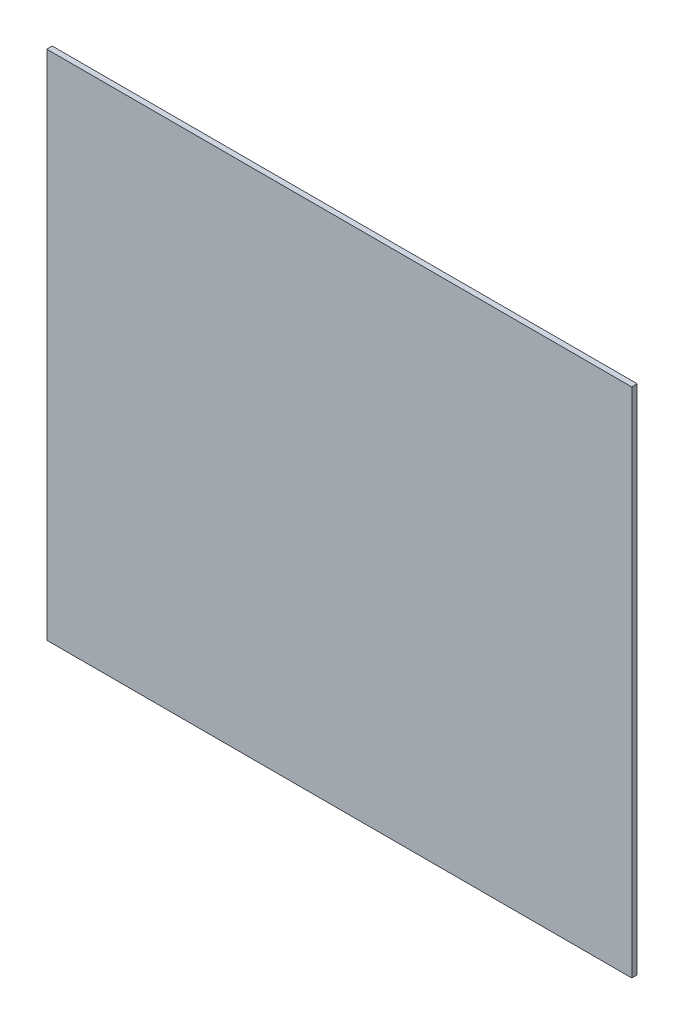
SolidWorks part; units mm, degrees
ref_plane "Front Plane" through (0, 0, 0) normal (0, 0, 1) x (1, 0, 0)
ref_plane "Top Plane" through (0, 0, 0) normal (0, 1, 0) x (1, 0, 0)
ref_plane "Right Plane" through (0, 0, 0) normal (1, 0, 0) x (0, 0, -1)
sketch "Sketch1" plane through (0, 0, 0) normal (0, 0, 1) x (1, 0, 0)
  line L1 (-160, -140) -> (160, -140)
  line L2 (-160, -140) -> (-160, 140)
  line L3 (-160, 140) -> (160, 140)
  line L4 (160, -140) -> (160, 140)
  line L5 (-160, -140) -> (160, 140) construction
  line L6 (-160, 140) -> (160, -140) construction
  point P0 (0, 0)
  dimension "D1" = 320
  dimension "D2" = 280
extrude "Boss-Extrude1" add sketch "Sketch1" along normal blind 3
equation "\"PCLength\"= 320mm'Length across I/O from PS to GPU"
equation "\"PCWidth\"= 242mm'Distance of longest part parallel to GPU(ussually GPU)"
equation "\"PCHeight\"= 172mm'Tallest point with mobo laying flat"
equation "\"WallThickness\"= 9mm'Thickness of each outer tank wall"
equation "\"ThermoBarrierThickness\"= 3mm'Thickness of barrier between hot side and cold side"
equation "\"HotSideGap\"= 40mm'Space in the hot side for a pump"
equation "\"PCClearance\"= 30mm'Clearance from top of tank to top of PC"
equation "\"RadiatorHeight\"= 275mm'Final Height from ground of radiators"
equation "\"D1@Sketch1\"=\"PCLength\""
equation "\"D2@Sketch1\"=\"RadiatorHeight\" + 5"
equation "\"D1@Boss-Extrude1\"=\"ThermoBarrierThickness\""
